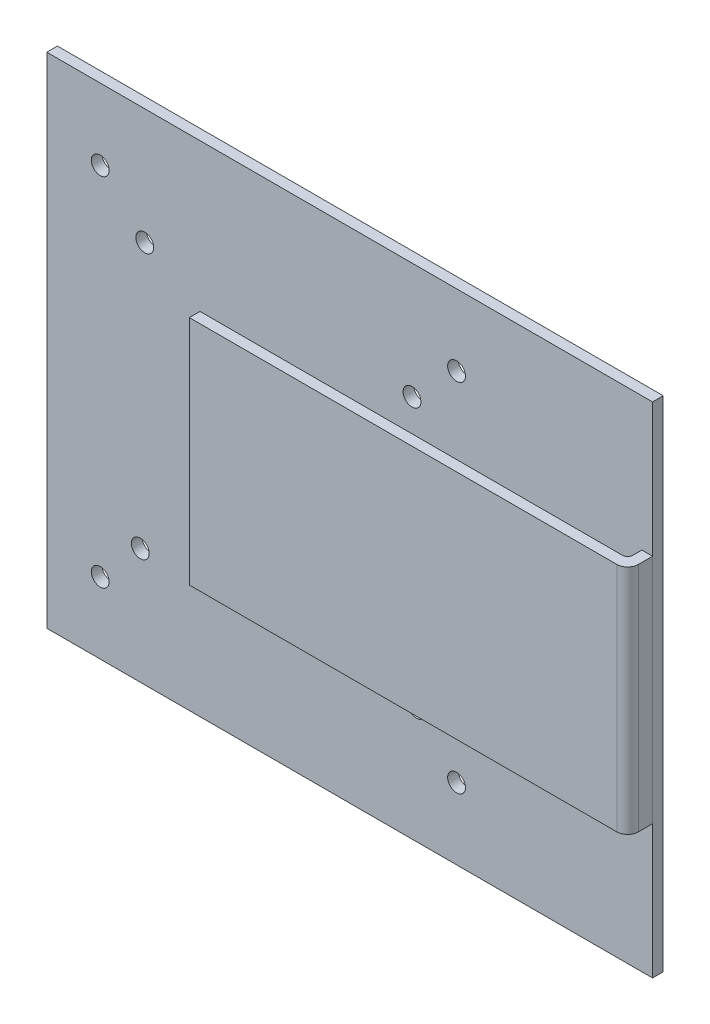
SolidWorks part; units mm, degrees
note: The reader was unsure of these and kept them because the rebuilt part matched: thickness of "Base-Flange1", "Sheet-Metal2", "Sheet-Metal6", "Sheet-Metal7", "Sheet-Metal11", "Sheet-Metal13", "Sheet-Metal14", "Sheet-Metal18", "Sheet-Metal23", "Sheet-Metal24".
material "ABS"
ref_plane "Front Plane" through (0, 0, 0) normal (0, 0, 1) x (1, 0, 0)
ref_plane "Top Plane" through (0, 0, 0) normal (0, 1, 0) x (1, 0, 0)
ref_plane "Right Plane" through (0, 0, 0) normal (1, 0, 0) x (0, 0, -1)
sketch "Sketch1" plane through (0, 0, 0) normal (0, 0, 1) x (1, 0, 0)
  line L5 (-75, -75) -> (75, -75)
  line L6 (-75, -75) -> (-75, 75)
  line L11 (-75, 75) -> (75, 75)
  line L12 (75, -75) -> (75, 75)
  line L17 (-75, -75) -> (75, 75) construction
  line L18 (-75, 75) -> (75, -75) construction
  point P0 (0, 0)
  dimension "D1" = 150
  dimension "D2" = 150
base flange "Base-Flange1" sketch "Sketch1" thickness 3 reverse thickness direction no parameters "D1"=0.7366
sketch "Sketch23" plane through (0, 0, -3) normal (0, 0, -1) x (-1, 0, 0)
  line L1 (75, -75) -> (-75, -75)
  line L2 (75, -75) -> (75, 75)
  line L3 (75, 75) -> (-75, 75)
  line L4 (-75, -75) -> (-75, 75)
  line L5 (75, -75) -> (-75, 75) construction
  line L6 (75, 75) -> (-75, -75) construction
  line L7 (70, -70) -> (-70, -70)
  line L8 (70, -70) -> (70, 70)
  line L9 (70, 70) -> (-70, 70)
  line L10 (-70, -70) -> (-70, 70)
  line L11 (70, -70) -> (-70, 70) construction
  line L12 (70, 70) -> (-70, -70) construction
  point P0 (0, 0)
  point P7 (0, 0)
  dimension "D1" = 140
extrude "Boss-Extrude3" add sketch "Sketch23" along normal blind 20
sketch "Sketch27" plane through (75, 0, 0) normal (1, 0, 0) x (0, 0, -1)
  line L0 (23, -75) -> (0, -75) construction
  line L1 (23, 75) -> (16, 75)
  line L2 (23, 75) -> (23, -75)
  line L3 (23, -75) -> (16, -75)
  line L4 (16, 75) -> (16, -75)
  dimension "D1" = 7
extrude "Boss-Extrude4" add sketch "Sketch27" along normal blind 20
sketch "Sketch31" plane through (0, 0, 0) normal (0, 0, 1) x (1, 0, 0)
  line L0 (75, -75) -> (75, 75) construction
  line L1 (75, 75) -> (-75, 75) construction
  line L2 (75, 75) -> (75, -75) construction
  line L3 (-75, -75) -> (75, -75) construction
  line L4 (-75, 75) -> (-75, -75) construction
  circle A0 centre (-50, -50) radius 2.5
  circle A1 centre (-50, 50) radius 2.5
  circle A2 centre (50, 50) radius 2.5
  circle A3 centre (50, -50) radius 2.5
  circle A4 centre (37.5, 37.5) radius 2.5
  circle A5 centre (-37.5, 37.5) radius 2.5
  circle A6 centre (38.7517, -37.4896) radius 2.5
  circle A7 centre (-38.7517, -37.4896) radius 2.5
  dimension "D1" = 5
  dimension "D2" = 5
  dimension "D3" = 5
  dimension "D4" = 5
  dimension "D5" = 25
  dimension "D6" = 25
  dimension "D7" = 25
  dimension "D8" = 25
  dimension "D9" = 25
  dimension "D10" = 25
  dimension "D11" = 25
  dimension "D12" = 25
  dimension "D13" = 37.5
  dimension "D14" = 37.5
  dimension "D15" = 37.5
  dimension "D16" = 37.5
  dimension "D17" = 75
  dimension "D18" = 75
extrude "Cut-Extrude1" cut sketch "Sketch31" against normal blind 20 normal cut yes
sketch "Sketch33" plane through (0, 0, -23) normal (0, 0, -1) x (-1, 0, 0)
  line L1 (-95, -75) -> (75, -75)
  line L2 (-95, -75) -> (-95, 75)
  line L3 (-95, 75) -> (75, 75)
  line L4 (75, -75) -> (75, 75)
extrude "Cut-Extrude3" cut sketch "Sketch33" against normal blind 20 normal cut yes
sketch "Sketch34" plane through (0, 0, 0) normal (0, 0, 1) x (1, 0, 0)
  line L1 (-65, 65) -> (65, 65)
  line L2 (-65, 65) -> (-65, -65)
  line L3 (-65, -65) -> (65, -65)
  line L4 (65, 65) -> (65, -65)
  line L5 (-65, 65) -> (65, -65) construction
  line L6 (-65, -65) -> (65, 65) construction
  line L11 (-75, 75) -> (75, 75)
  line L12 (-75, 75) -> (-75, -75)
  line L13 (-75, -75) -> (75, -75)
  line L14 (75, 75) -> (75, -75)
  line L15 (-75, 75) -> (75, -75) construction
  line L16 (-75, -75) -> (75, 75) construction
  point P0 (0, 0)
  point P5 (0, 0)
extrude "Cut-Extrude4" cut sketch "Sketch34" against normal blind 20 normal cut yes
ref_plane "Plane1" through (0, 32.5, 0) normal (0, 1, 0) x (1, 0, 0)
sketch "Sketch36" plane through (0, 32.5, 0) normal (0, 1, 0) x (1, 0, 0)
  line L1 (64.9088, 2.9798) -> (61.9088, 2.9798)
  line L2 (64.9088, 2.9798) -> (64.9088, 8.9798)
  line L3 (64.9088, 8.9798) -> (61.9088, 8.9798)
  line L4 (61.9088, 2.9798) -> (61.9088, 8.9798)
  dimension "D1" = 6
  dimension "D2" = 3
sketch "Sketch39" plane through (0, 0, 0) normal (0, 0, 1) x (1, 0, 0)
  line L1 (65, 65) -> (105, 65)
  line L2 (65, 65) -> (65, -65)
  line L3 (65, -65) -> (105, -65)
  line L4 (105, 65) -> (105, -65)
  dimension "D1" = 40
extrude "Boss-Extrude11" add sketch "Sketch39" against normal blind 3
sketch "Sketch46" plane through (105, 0, 0) normal (1, 0, 0) x (0, 0, -1)
  line L0 (0, 0) -> (0, 32.5)
  line L1 (0, -65) -> (0, 65) construction
  line L2 (0, 32.5) -> (-7, 32.5)
  line L3 (-7, 32.5) -> (-7, -32.5)
  line L4 (-7, -32.5) -> (0, -32.5)
  line L5 (0, -32.5) -> (0, 0)
  dimension "D1" = 32.5
  dimension "D2" = 7
  dimension "D3" = 65
extrude "Boss-Extrude14" add sketch "Sketch46" against normal blind 3 separate body
sketch "Sketch47" plane through (102, 0, 0) normal (-1, 0, 0) x (0, 0, 1)
  line L0 (7, -32.5) -> (0, -32.5) construction
  line L1 (7, 32.5) -> (4, 32.5)
  line L2 (7, 32.5) -> (7, -32.5)
  line L3 (7, -32.5) -> (4, -32.5)
  line L4 (4, 32.5) -> (4, -32.5)
  dimension "D1" = 3
extrude "Boss-Extrude15" add sketch "Sketch47" along normal blind 120
fillet "Fillet3" radius 1.5 1 edges at (102, 0, 4)
fillet "Fillet4" radius 3 1 edges at (105, 0, 7)
sketch "Sketch48" plane through (0, -65, 0) normal (0, -1, 0) x (-1, 0, 0)
  line L1 (-105, 0) -> (65, 0)
  line L2 (-105, 0) -> (-105, 3)
  line L3 (-105, 3) -> (65, 3)
  line L4 (65, 0) -> (65, 3)
extrude "Boss-Extrude16" add sketch "Sketch48" along normal blind 5
sketch "Sketch49" plane through (0, 65, 0) normal (0, 1, 0) x (1, 0, 0)
  line L1 (105, 3) -> (-65, 3)
  line L2 (105, 3) -> (105, 0)
  line L3 (105, 0) -> (-65, 0)
  line L4 (-65, 3) -> (-65, 0)
extrude "Boss-Extrude17" add sketch "Sketch49" along normal blind 5
sketch "Bend-Lines1" [suppressed] plane through (0, 0, 0) normal (0, 1, 0) x (1, 0, 0)
sketch "Bounding-Box1" [suppressed] plane through (0, 0, 0) normal (0, 1, 0) x (1, 0, 0)
sheet metal parameters "Sheet-Metal2" thickness 3 parameters "D1"=0.7366
flat pattern "Flat-Pattern2" [suppressed]
sketch "Bend-Lines2" plane through (0, 0, 0) normal (0, 1, 0) x (1, 0, 0)
sketch3d "Bounding-Box2" [suppressed]
  line L0 (-65, -65, 0) -> (65, -65, 0) construction
  line L1 (-65, 65, 0) -> (65, 65, 0) construction
  line L2 (-65, -65, 0) -> (-65, 65, 0) construction
  line L3 (65, -65, 0) -> (65, 65, 0) construction
sketch "Sketch23-1" [suppressed] plane through (0, 0, -3) normal (0, 0, -1) x (-1, 0, 0)
  line L1 (65, -65) -> (-65, -65)
  line L2 (65, -65) -> (65, 65)
  line L3 (65, 65) -> (-65, 65)
  line L4 (-65, -65) -> (-65, 65)
  line L5 (65, -65) -> (-65, 65) construction
  line L6 (65, 65) -> (-65, -65) construction
  line L7 (65, -65) -> (-65, -65)
  line L8 (65, -65) -> (65, 65)
  line L9 (65, 65) -> (-65, 65)
  line L10 (-65, -65) -> (-65, 65)
  line L11 (65, -65) -> (-65, 65) construction
  line L12 (65, 65) -> (-65, -65) construction
  point P0 (0, 0)
  point P7 (0, 0)
  dimension "D1" = 130
sheet metal parameters "Sheet-Metal6" thickness 3 parameters "D1"=0.7366, "D7"=10
flat pattern "Flat-Pattern2" [suppressed]
sketch "Bend-Lines2" plane through (0, 0, 0) normal (0, 1, 0) x (1, 0, 0)
sketch3d "Bounding-Box2" [suppressed]
  line L0 (-75, -75, 0) -> (75, -75, 0) construction
  line L1 (-75, 75, 0) -> (75, 75, 0) construction
  line L2 (-75, -75, 0) -> (-75, 75, 0) construction
  line L3 (75, -75, 0) -> (75, 75, 0) construction
sketch "Sketch23-1" [suppressed] plane through (0, 0, -7) normal (0, 0, -1) x (-1, 0, 0)
  line L1 (75, -75) -> (-75, -75)
  line L2 (75, -75) -> (75, 75)
  line L3 (75, 75) -> (-75, 75)
  line L4 (-75, -75) -> (-75, 75)
  line L5 (75, -75) -> (-75, 75) construction
  line L6 (75, 75) -> (-75, -75) construction
  line L7 (65, -65) -> (-65, -65)
  line L8 (65, -65) -> (65, 65)
  line L9 (65, 65) -> (-65, 65)
  line L10 (-65, -65) -> (-65, 65)
  line L11 (65, -65) -> (-65, 65) construction
  line L12 (65, 65) -> (-65, -65) construction
  point P0 (0, 0)
  point P7 (0, 0)
  dimension "D1" = 130
sheet metal parameters "Sheet-Metal7" thickness 3 parameters "D1"=0.7366, "D7"=10
flat pattern "Flat-Pattern2" [suppressed]
sketch "Bend-Lines2" plane through (0, 0, 0) normal (0, 1, 0) x (1, 0, 0)
sketch3d "Bounding-Box2" [suppressed]
  line L0 (-75, -75, 0) -> (75, -75, 0) construction
  line L1 (-75, 75, 0) -> (75, 75, 0) construction
  line L2 (-75, -75, 0) -> (-75, 75, 0) construction
  line L3 (75, -75, 0) -> (75, 75, 0) construction
sketch "Sketch23-1" [suppressed] plane through (0, 0, -7) normal (0, 0, -1) x (-1, 0, 0)
  line L1 (75, -75) -> (-75, -75)
  line L2 (75, -75) -> (75, 75)
  line L3 (75, 75) -> (-75, 75)
  line L4 (-75, -75) -> (-75, 75)
  line L5 (75, -75) -> (-75, 75) construction
  line L6 (75, 75) -> (-75, -75) construction
  line L7 (65, -65) -> (-65, -65)
  line L8 (65, -65) -> (65, 65)
  line L9 (65, 65) -> (-65, 65)
  line L10 (-65, -65) -> (-65, 65)
  line L11 (65, -65) -> (-65, 65) construction
  line L12 (65, 65) -> (-65, -65) construction
  point P0 (0, 0)
  point P7 (0, 0)
  dimension "D1" = 130
sheet metal parameters "Sheet-Metal11" thickness 3 parameters "D1"=0.7366, "D7"=10
flat pattern "Flat-Pattern2" [suppressed]
sketch "Bend-Lines2" plane through (0, 0, 0) normal (0, 1, 0) x (1, 0, 0)
sketch3d "Bounding-Box2" [suppressed]
  line L0 (-75, -75, 0) -> (75, -75, 0) construction
  line L1 (-75, 75, 0) -> (75, 75, 0) construction
  line L2 (-75, -75, 0) -> (-75, 75, 0) construction
  line L3 (75, -75, 0) -> (75, 75, 0) construction
sketch "Sketch23-1" plane through (0, 0, -3) normal (0, 0, -1) x (-1, 0, 0)
  line L1 (75, -75) -> (-75, -75)
  line L2 (75, -75) -> (75, 75)
  line L3 (75, 75) -> (-75, 75)
  line L4 (-75, -75) -> (-75, 75)
  line L5 (75, -75) -> (-75, 75) construction
  line L6 (75, 75) -> (-75, -75) construction
  line L7 (65, -65) -> (-65, -65)
  line L8 (65, -65) -> (65, 65)
  line L9 (65, 65) -> (-65, 65)
  line L10 (-65, -65) -> (-65, 65)
  line L11 (65, -65) -> (-65, 65) construction
  line L12 (65, 65) -> (-65, -65) construction
  point P0 (0, 0)
  point P7 (0, 0)
  dimension "D1" = 130
sheet metal parameters "Sheet-Metal13" thickness 3 parameters "D1"=0.7366, "D7"=10
flat pattern "Flat-Pattern2" [suppressed]
sketch "Bend-Lines2" plane through (0, 0, 0) normal (0, 1, 0) x (1, 0, 0)
sketch3d "Bounding-Box2" [suppressed]
  line L0 (-75, -75, 0) -> (75, -75, 0) construction
  line L1 (-75, 75, 0) -> (75, 75, 0) construction
  line L2 (-75, -75, 0) -> (-75, 75, 0) construction
  line L3 (75, -75, 0) -> (75, 75, 0) construction
sketch "Sketch23-1" [suppressed] plane through (0, 0, -3) normal (0, 0, -1) x (-1, 0, 0)
  line L1 (75, -75) -> (-75, -75)
  line L2 (75, -75) -> (75, 75)
  line L3 (75, 75) -> (-75, 75)
  line L4 (-75, -75) -> (-75, 75)
  line L5 (75, -75) -> (-75, 75) construction
  line L6 (75, 75) -> (-75, -75) construction
  line L7 (65, -65) -> (-65, -65)
  line L8 (65, -65) -> (65, 65)
  line L9 (65, 65) -> (-65, 65)
  line L10 (-65, -65) -> (-65, 65)
  line L11 (65, -65) -> (-65, 65) construction
  line L12 (65, 65) -> (-65, -65) construction
  point P0 (0, 0)
  point P7 (0, 0)
  dimension "D1" = 130
sheet metal parameters "Sheet-Metal14" thickness 3 parameters "D1"=0.7366, "D7"=10
flat pattern "Flat-Pattern2" [suppressed]
sketch "Bend-Lines2" plane through (0, 0, 0) normal (0, 1, 0) x (1, 0, 0)
sketch3d "Bounding-Box2" [suppressed]
  line L0 (-65, -65, 0) -> (65, -65, 0) construction
  line L1 (-65, 65, 0) -> (65, 65, 0) construction
  line L2 (-65, -65, 0) -> (-65, 65, 0) construction
  line L3 (65, -65, 0) -> (65, 65, 0) construction
sketch "Sketch23-1" [suppressed] plane through (0, 0, -3) normal (0, 0, -1) x (-1, 0, 0)
  line L1 (75, -75) -> (-75, -75)
  line L2 (75, -75) -> (75, 75)
  line L3 (75, 75) -> (-75, 75)
  line L4 (-75, -75) -> (-75, 75)
  line L5 (75, -75) -> (-75, 75) construction
  line L6 (75, 75) -> (-75, -75) construction
  line L7 (65, -65) -> (-65, -65)
  line L8 (65, -65) -> (65, 65)
  line L9 (65, 65) -> (-65, 65)
  line L10 (-65, -65) -> (-65, 65)
  line L11 (65, -65) -> (-65, 65) construction
  line L12 (65, 65) -> (-65, -65) construction
  point P0 (0, 0)
  point P7 (0, 0)
  dimension "D1" = 130
sheet metal parameters "Sheet-Metal18" thickness 3 parameters "D1"=0.7366, "D7"=10
flat pattern "Flat-Pattern2" [suppressed]
sketch "Bend-Lines2" plane through (0, 0, 0) normal (0, 1, 0) x (1, 0, 0)
sketch3d "Bounding-Box2" [suppressed]
  line L0 (-65, -65, 0) -> (105, -65, 0) construction
  line L1 (-65, 65, 0) -> (105, 65, 0) construction
  line L2 (-65, -65, 0) -> (-65, 65, 0) construction
  line L3 (105, -65, 0) -> (105, 65, 0) construction
sketch "Sketch23-1" [suppressed] plane through (0, 0, -3) normal (0, 0, -1) x (-1, 0, 0)
  line L1 (75, -75) -> (-75, -75)
  line L2 (75, -75) -> (75, 75)
  line L3 (75, 75) -> (-75, 75)
  line L4 (-75, -75) -> (-75, 75)
  line L5 (75, -75) -> (-75, 75) construction
  line L6 (75, 75) -> (-75, -75) construction
  line L7 (70, -70) -> (-70, -70)
  line L8 (70, -70) -> (70, 70)
  line L9 (70, 70) -> (-70, 70)
  line L10 (-70, -70) -> (-70, 70)
  line L11 (70, -70) -> (-70, 70) construction
  line L12 (70, 70) -> (-70, -70) construction
  point P0 (0, 0)
  point P7 (0, 0)
  dimension "D1" = 140
sheet metal parameters "Sheet-Metal23" thickness 3 parameters "D1"=0.7366, "D7"=10
flat pattern "Flat-Pattern2" [suppressed]
sketch "Bend-Lines2" plane through (0, 0, 0) normal (0, 1, 0) x (1, 0, 0)
sketch3d "Bounding-Box2" [suppressed]
  line L0 (-65, -70, 0) -> (105, -70, 0) construction
  line L1 (-65, 65, 0) -> (105, 65, 0) construction
  line L2 (-65, -70, 0) -> (-65, 65, 0) construction
  line L3 (105, -70, 0) -> (105, 65, 0) construction
sketch "Sketch23-1" [suppressed] plane through (0, 0, -3) normal (0, 0, -1) x (-1, 0, 0)
  line L1 (75, -75) -> (-75, -75)
  line L2 (75, -75) -> (75, 75)
  line L3 (75, 75) -> (-75, 75)
  line L4 (-75, -75) -> (-75, 75)
  line L5 (75, -75) -> (-75, 75) construction
  line L6 (75, 75) -> (-75, -75) construction
  line L7 (70, -70) -> (-70, -70)
  line L8 (70, -70) -> (70, 70)
  line L9 (70, 70) -> (-70, 70)
  line L10 (-70, -70) -> (-70, 70)
  line L11 (70, -70) -> (-70, 70) construction
  line L12 (70, 70) -> (-70, -70) construction
  point P0 (0, 0)
  point P7 (0, 0)
  dimension "D1" = 140
sheet metal parameters "Sheet-Metal24" thickness 3 parameters "D1"=0.7366, "D7"=10
flat pattern "Flat-Pattern2" [suppressed]
sketch "Bend-Lines2" plane through (0, 0, 0) normal (0, 1, 0) x (1, 0, 0)
sketch3d "Bounding-Box2" [suppressed]
  line L0 (-65, -70, 0) -> (105, -70, 0) construction
  line L1 (-65, 70, 0) -> (105, 70, 0) construction
  line L2 (-65, -70, 0) -> (-65, 70, 0) construction
  line L3 (105, -70, 0) -> (105, 70, 0) construction
sketch "Sketch23-1" [suppressed] plane through (0, 0, -3) normal (0, 0, -1) x (-1, 0, 0)
  line L1 (75, -75) -> (-75, -75)
  line L2 (75, -75) -> (75, 75)
  line L3 (75, 75) -> (-75, 75)
  line L4 (-75, -75) -> (-75, 75)
  line L5 (75, -75) -> (-75, 75) construction
  line L6 (75, 75) -> (-75, -75) construction
  line L7 (70, -70) -> (-70, -70)
  line L8 (70, -70) -> (70, 70)
  line L9 (70, 70) -> (-70, 70)
  line L10 (-70, -70) -> (-70, 70)
  line L11 (70, -70) -> (-70, 70) construction
  line L12 (70, 70) -> (-70, -70) construction
  point P0 (0, 0)
  point P7 (0, 0)
  dimension "D1" = 140
